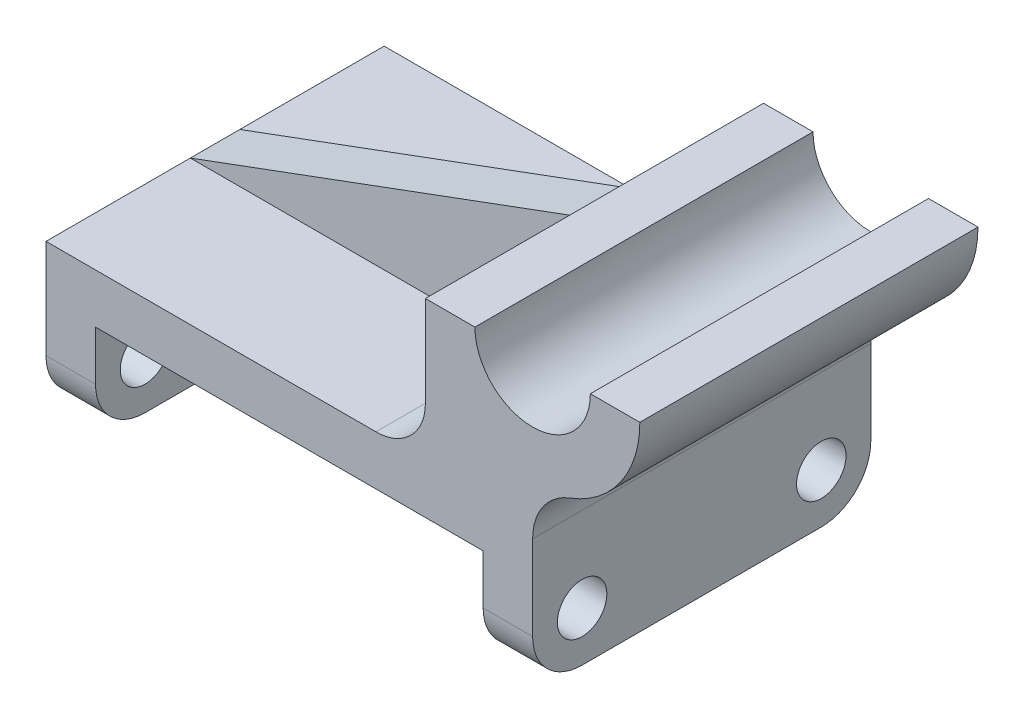
SolidWorks part; units mm, degrees
ref_plane "Front Plane" through (0, 0, 0) normal (0, 0, 1) x (1, 0, 0)
ref_plane "Top Plane" through (0, 0, 0) normal (0, 1, 0) x (1, 0, 0)
ref_plane "Right Plane" through (0, 0, 0) normal (1, 0, 0) x (0, 0, -1)
sketch "Sketch1" plane through (0, 0, 0) normal (0, 0, 1) x (1, 0, 0)
  line L0 (118, 7.1152) -> (118, 41.1152) construction
  line L1 (12, -4.8848) -> (106, -4.8848)
  line L2 (0, 0) -> (0, 7.1152)
  line L3 (0, 7.1152) -> (80, 7.1152)
  line L4 (118, 0) -> (118, 7.1152)
  line L6 (0, 0) -> (0, -28.8848)
  line L7 (0, -28.8848) -> (12, -28.8848)
  line L8 (12, -4.8848) -> (12, -28.8848)
  line L10 (118, 0) -> (118, -28.8848)
  line L11 (118, -28.8848) -> (106, -28.8848)
  line L12 (106, -4.8848) -> (106, -28.8848)
  line L13 (118, 7.1152) -> (118, 3.6452)
  line L14 (92, 41.1152) -> (144, 41.1152)
  line L15 (92, 41.1152) -> (92, 19.1152)
  line L16 (0, 7.1152) -> (92, 41.1152)
  arc A0 (127.1, 16.7597) -> (144, 41.1152) centre (118, 41.1152) ccw
  arc A1 (104, 41.1152) -> (132, 41.1152) centre (118, 41.1152) ccw
  arc A2 (118, 3.6452) -> (127.1, 16.7597) centre (132, 3.6452) cw
  arc A3 (80, 7.1152) -> (92, 19.1152) centre (80, 19.1152) ccw
  point P21 (118, 15.1152)
  dimension "D6" = 14
  dimension "D2" = 12
  dimension "D8" = 14
  dimension "D9" = 26
  dimension "D1" = 36
  dimension "D3" = 118
  dimension "D4" = 94
  dimension "D5" = 12
  dimension "D7" = 70
  dimension "D10" = 12
  dimension "D11" = 12
extrude "Boss-Extrude1" add sketch "Sketch1" along normal mid plane 82 contours L4 L0 A1 L14 L15 A3 L3 L2 L6 L7 L8 L1 L12 L11 L10 | L0 L4 A2 A0 L14 A1 region at (71.1445, 2.9276, 0) region at (130.4891, 27.1362, 0)
extrude "Boss-Extrude2" add sketch "Sketch1<3>" along normal mid plane 12 contours L3 A3 L15 L16 region at (60.7692, 18.6229, 0)
sketch "Sketch1<3>" plane through (0, 0, 0) normal (0, 0, 1) x (1, 0, 0) same geometry as "Sketch1"
sketch "Sketch2" plane through (118, 0, 0) normal (1, 0, 0) x (0, 0, -1)
  line L0 (-41, -28.8848) -> (41, -28.8848) construction
  line L1 (-41, -28.8848) -> (-41, 3.6452) construction
  line L2 (0, -28.8848) -> (0, 3.6452) construction
  line L3 (-41, 3.6452) -> (41, 3.6452) construction
  circle A0 centre (-29, -16.8848) radius 6
  circle A1 centre (29, -16.8848) radius 6
  dimension "D3" = 12
  dimension "D1" = 12
  dimension "D2" = 12
extrude "Cut-Extrude1" cut sketch "Sketch2" against normal through all and the other way through all
fillet "Fillet1" radius 12 4 edges at (6, -28.8848, -41) (6, -28.8848, 41) (112, -28.8848, -41) (112, -28.8848, 41)
